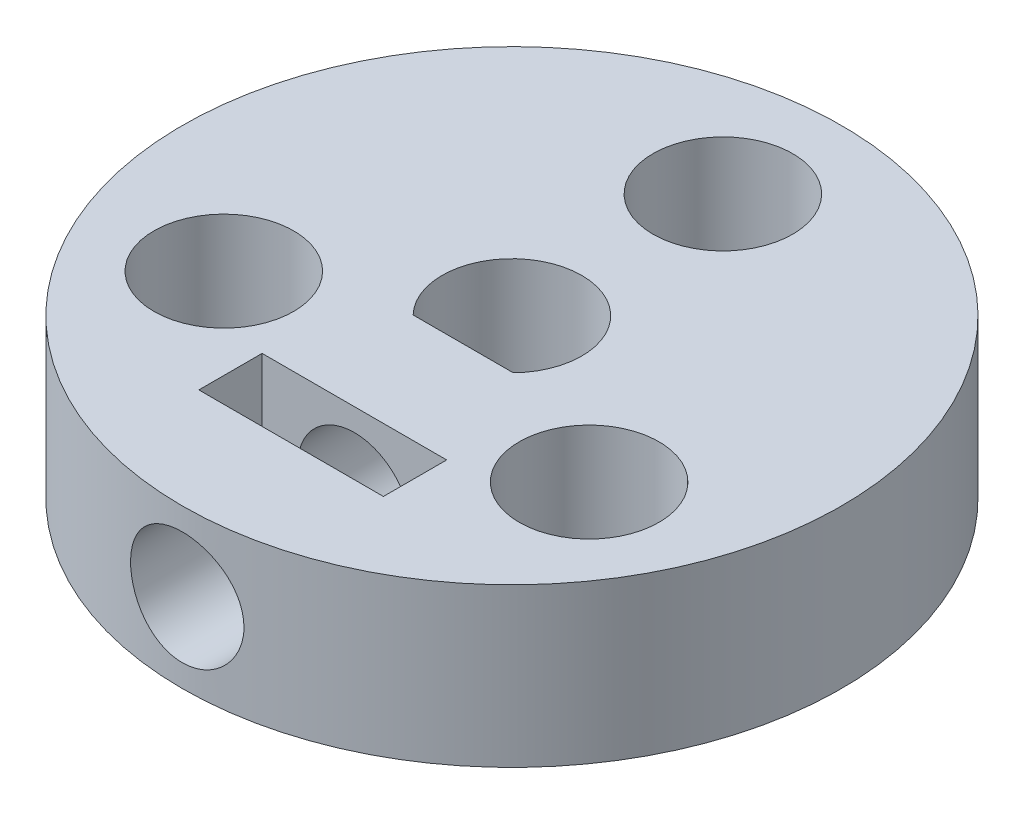
SolidWorks part; units mm, degrees
ref_plane "Front Plane" through (0, 0, 0) normal (0, 0, 1) x (1, 0, 0)
ref_plane "Top Plane" through (0, 0, 0) normal (0, 1, 0) x (1, 0, 0)
ref_plane "Right Plane" through (0, 0, 0) normal (1, 0, 0) x (0, 0, -1)
sketch "Sketch1" plane through (0, 0, 0) normal (0, 1, 0) x (1, 0, 0)
  circle A0 centre (0, 0) radius 12.5
  dimension "D1" = 25
extrude "Boss-Extrude1" add sketch "Sketch1" along normal blind 6
sketch "Sketch2" plane through (0, 6, 0) normal (0, 1, 0) x (1, 0, 0)
  line L0 (-1.8974, -1.85) -> (1.8974, -1.85)
  line L1 (0, -1.85) -> (0, 2.65) construction
  circle A0 centre (0, 0) radius 2.65
  dimension "D1" = 5.3
  dimension "D2" = 4.5
extrude "Cut-Extrude1" cut sketch "Sketch2" against normal up to next contours L0 L1 A0 | L1 L0 A0 region at (-1.1663, 6, -0.2281) region at (1.1663, 6, -0.2281)
sketch "Sketch3" plane through (0, 6, 0) normal (0, 1, 0) x (1, 0, 0)
  line L0 (0, -1.85) -> (0, -12.5) construction
  line L1 (-1.8974, -1.85) -> (1.8974, -1.85) construction
  line L3 (-3.5, -8.375) -> (3.5, -8.375)
  line L4 (-3.5, -8.375) -> (-3.5, -5.975)
  line L5 (-3.5, -5.975) -> (3.5, -5.975)
  line L6 (3.5, -8.375) -> (3.5, -5.975)
  line L7 (-3.5, -8.375) -> (3.5, -5.975) construction
  line L8 (-3.5, -5.975) -> (3.5, -8.375) construction
  circle A0 centre (0, 0) radius 12.5 construction
  point P7 (0, -7.175)
  dimension "D1" = 2.4
  dimension "D2" = 7
extrude "Cut-Extrude2" cut sketch "Sketch3" against normal up to next
sketch "Sketch4" plane through (0, 0, 1.85) normal (0, 0, -1) x (-1, 0, 0)
  line L0 (0, 0) -> (0, 6) construction
  line L1 (-1.8974, 0) -> (1.8974, 0) construction
  line L2 (1.8974, 6) -> (-1.8974, 6) construction
  circle A0 centre (0, 3) radius 2.15
  dimension "D1" = 4.3
extrude "Cut-Extrude3" cut sketch "Sketch4" against normal through all and the other way blind 1
sketch "Sketch5" plane through (0, 6, 0) normal (0, 1, 0) x (1, 0, 0)
  line L0 (0, 12.5) -> (0, 0) construction
  circle A2 centre (0, 8) radius 2.65
  circle A5 centre (0, 0) radius 12.5 construction
  circle A6 centre (6.9282, -4) radius 2.65
  circle A7 centre (-6.9282, -4) radius 2.65
  point P14 (0, 0)
  dimension "D1" = 5.3
  dimension "D3" = 4
  dimension "D4" = 6.9282
  dimension "D5" = 8
  dimension "D2" = 3
extrude "Cut-Extrude4" cut sketch "Sketch5" against normal through all
